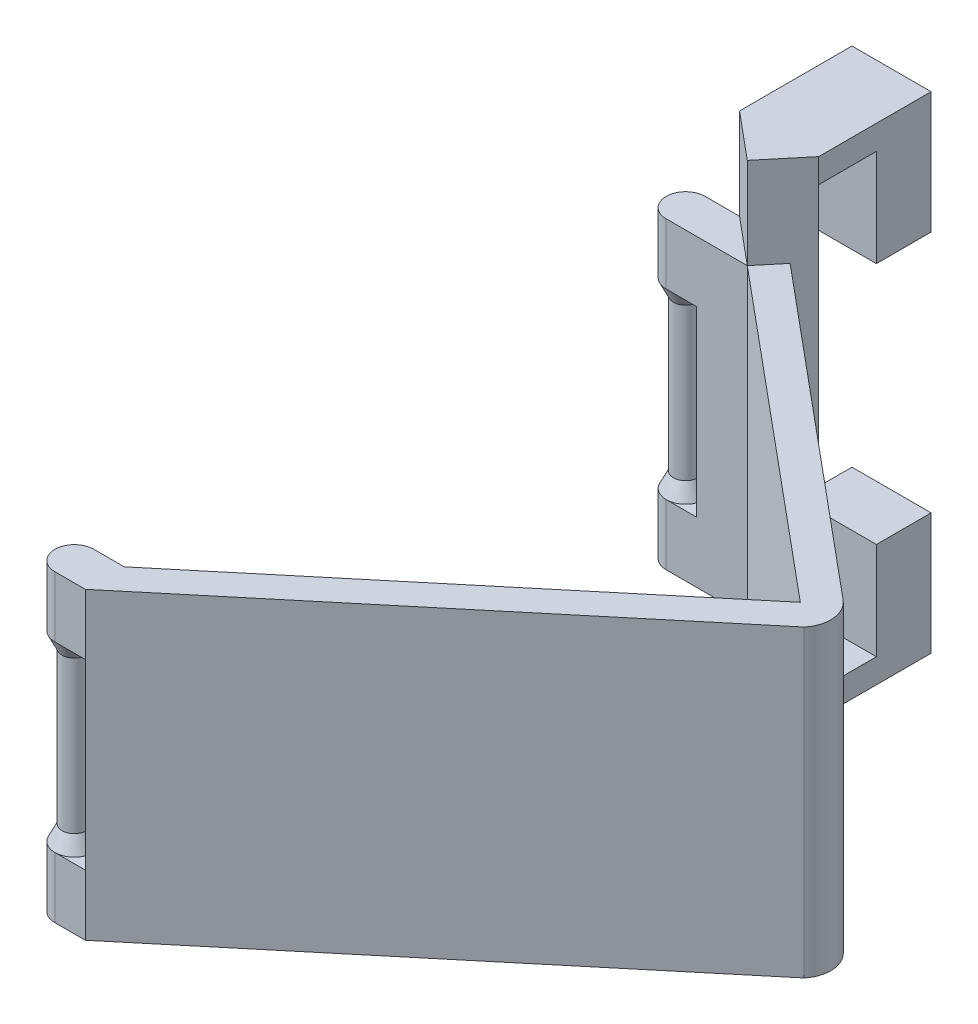
SolidWorks part; units mm, degrees
ref_plane "前视基准面" through (0, 0, 0) normal (0, 0, 1) x (1, 0, 0)
ref_plane "上视基准面" through (0, 0, 0) normal (0, 1, 0) x (1, 0, 0)
ref_plane "右视基准面" through (0, 0, 0) normal (1, 0, 0) x (0, 0, -1)
sketch "草图1" plane through (0, 0, 0) normal (0, 1, 0) x (1, 0, 0)
  line L0 (0, 0) -> (0, 50)
  line L1 (0, 0) -> (-0.664, -50.5533)
  line L2 (0, 0) -> (60, 0)
  line L3 (60, 0) -> (-0.664, -50.5533)
  line L4 (0, 50) -> (60, 0)
  line L5 (60, 0) -> (63.2009, 3.8411)
  line L6 (63.2009, 3.8411) -> (7.8102, 50)
  line L7 (60, 0) -> (63.8411, -3.2009)
  line L8 (63.8411, -3.2009) -> (7.6822, -50)
  line L9 (0, 50) -> (7.8102, 50)
  line L11 (7.6822, -50) -> (-0.664, -56.9551)
  line L12 (-0.664, -56.9551) -> (-0.664, -50.5533)
  arc A0 (63.2009, 3.8411) -> (63.8411, -3.2009) centre (60, 0) cw
extrude "凸台-拉伸1" add sketch "草图1" along normal blind 50 contours L3 L8 L7 | A0 L5 L7 | L9 L4 L5 L6 region at (32.7161, 0, -25.9475) region at (30.6381, 0, 27.7019) region at (62.9887, 0, -0.2717)
sketch "草图3" plane through (27.7911, 0, -33.3493) normal (0.6402, 0, -0.7682) x (-0.7682, 0, -0.6402)
  line L0 (-46.0933, 25) -> (26.0092, 25) construction
  line L1 (-46.0933, 50) -> (-46.0933, 0) construction
  line L2 (26.0092, 50) -> (26.0092, 0) construction
ref_plane "基准面1" through (0, 25, 0) normal (0, -1, 0) x (-0.7682, 0, -0.6402)
sketch "草图4" plane through (0, 50, 0) normal (0, 1, 0) x (1, 0, 0)
  line L0 (0, 50) -> (7.6822, 43.5982)
  line L1 (0, 50) -> (60, 0) construction
  line L2 (7.6822, 43.5982) -> (10.8831, 47.4393)
  line L3 (63.2009, 3.8411) -> (7.8102, 50) construction
  line L4 (10.8831, 47.4393) -> (7.8102, 50)
  line L5 (7.8102, 50) -> (0, 50)
  line L6 (7.8102, 50) -> (19.6167, 50)
  line L7 (10.8831, 47.4393) -> (13.0171, 50)
  line M4 (63.2009, 3.8411) -> (7.8102, 50)
  line M5 (7.8102, 50) -> (0, 50)
  line M6 (0, 50) -> (60, 0)
extrude "凸台-拉伸3" add sketch "草图4" along normal blind 15 and the other way blind 50 contours L2 M6 M4 M5 | L7 L6 M4 region at (6.2006, 50, -47.6222) region at (10.5702, 50, -49.1464)
sketch "草图5" plane through (0, 0, -50) normal (0, 0, -1) x (-1, 0, 0)
  line L0 (-13.0171, 65) -> (-13.0171, 61)
  line L1 (-13.0171, 0) -> (-13.0171, 65) construction
  line L2 (-13.0171, 61) -> (0, 61)
  line L3 (0, 65) -> (0, 0) construction
  line L4 (0, 61) -> (0, 65)
  line L5 (0, 65) -> (-13.0171, 65)
extrude "凸台-拉伸4" add sketch "草图5" along normal blind 18.5
sketch "草图6" plane through (0, 61, 0) normal (0, -1, 0) x (1, 0, 0)
  line L0 (0, -68.5) -> (0, -59.5)
  line L1 (0, -68.5) -> (0, -50) construction
  line L2 (13.0171, -68.5) -> (0, -68.5) construction
  line L3 (0, -59.5) -> (13.0171, -59.5)
  line L4 (13.0171, -68.5) -> (13.0171, -50) construction
  line L5 (13.0171, -59.5) -> (13.0171, -68.5)
  line L6 (13.0171, -68.5) -> (0, -68.5)
extrude "凸台-拉伸5" add sketch "草图6" along normal blind 16
mirror "镜向4" about plane through (0, 25, 0) normal (0, -1, 0) of "凸台-拉伸5", "凸台-拉伸3", "凸台-拉伸4"
sketch "草图7" plane through (0, 50, 0) normal (0, 1, 0) x (1, 0, 0)
  line L0 (-0.664, -53.7542) -> (-5.664, -53.7542)
  line L1 (-0.664, -56.9551) -> (-0.664, -50.5533) construction
  line L2 (-5.664, -53.7542) -> (-5.664, 89.3377)
sketch "草图8" plane through (0, 50, 0) normal (0, 1, 0) x (1, 0, 0)
  line L0 (-0.664, -50.5533) -> (-0.664, 65.3859)
  line L1 (7.6822, 43.5982) -> (-0.664, 43.5982)
  line L2 (-0.664, 43.5982) -> (-0.664, 50)
  line L3 (-0.664, 50) -> (0, 50)
  line L4 (0, 50) -> (7.6822, 43.5982)
extrude "凸台-拉伸6" add sketch "草图8" against normal blind 50 contours L1 L2 L3 L4
sketch "草图9" plane through (0, 0, 0) normal (0, -1, 0) x (1, 0, 0)
  line L0 (-0.664, 56.9551) -> (-5.664, 56.9551)
  line L1 (-0.664, 50.5533) -> (-5.664, 50.5533)
  line L2 (-5.664, 53.7542) -> (-5.664, -89.3377) construction
  line L3 (-0.664, 56.9551) -> (-0.664, 50.5533)
  line L4 (-5.664, 56.9551) -> (-5.664, 50.5533)
  arc A0 (-5.664, 56.9551) -> (-5.664, 50.5533) centre (-5.664, 53.7542) ccw
  line M5 (-0.664, 56.9551) -> (-0.664, 50.5533)
extrude "凸台-拉伸7" add sketch "草图9" against normal blind 10 contours L0 L4 L1 M5 | L4 A0 region at (-3.164, 0, 53.7542) region at (-7.0225, 0, 53.7542)
sketch "草图10" plane through (0, 0, 0) normal (0, -1, 0) x (1, 0, 0)
  line L0 (-0.664, -43.5982) -> (-5.664, -43.5982)
  line L1 (-5.664, 53.7542) -> (-5.664, -89.3377) construction
  line L2 (-0.664, -50) -> (-5.664, -50)
  line L3 (-5.664, -43.5982) -> (-5.664, -50)
  arc A0 (-5.664, -43.5982) -> (-5.664, -50) centre (-5.664, -46.7991) ccw
  line M3 (-0.664, -43.5982) -> (-0.664, -50)
extrude "凸台-拉伸8" add sketch "草图10" against normal blind 10 contours L0 L3 L2 M3 | L3 A0 region at (-3.164, 0, -46.7991) region at (-7.0225, 0, -46.7991)
mirror "镜向5" about plane through (0, 25, 0) normal (0, -1, 0) of "凸台-拉伸8", "凸台-拉伸7"
sketch "草图11" plane through (0, 40, 0) normal (0, -1, 0) x (1, 0, 0)
  circle A0 centre (-5.664, 53.7542) radius 2
extrude "凸台-拉伸9" add sketch "草图11" along normal blind 30
ref_plane "基准面3" through (0, 0, 53.7542) normal (0, 0, -1) x (-1, 0, 0)
sketch "草图14" plane through (0, 0, 53.7542) normal (0, 0, -1) x (-1, 0, 0)
  line L5 (7.664, 10) -> (8.8649, 10)
  line L6 (7.664, 10) -> (7.664, 12.5)
  line L7 (7.664, 10) -> (7.664, 40) construction
  line L8 (7.664, 12.5) -> (8.8649, 10)
ref_axis "基准轴2" through (-5.664, 10, 53.7542) along (0, 1, 0)
revolve "旋转1" add sketch "草图14" angle 360 about axis through (-5.664, 10, 53.7542) along (0, 1, 0) region at (-8.0643, 10.8333, 53.7542)
mirror "镜向6" about plane through (0, 25, 0) normal (0, -1, 0) of "旋转1"
sketch "草图15" plane through (0, 10, 0) normal (0, 1, 0) x (1, 0, 0)
  circle A0 centre (-5.664, 46.7991) radius 2
extrude "凸台-拉伸10" add sketch "草图15" along normal blind 30
sketch "草图16" plane through (0, 0, 0) normal (0, -1, 0) x (1, 0, 0)
  line L0 (-5.664, -46.7991) -> (2.4555, -46.7991)
ref_plane "基准面4" through (0, 0, -46.7991) normal (0, 0, 1) x (1, 0, 0)
ref_axis "基准轴3" through (-5.664, 40, -46.7991) along (0, -1, 0)
sketch "草图17" plane through (0, 0, -46.7991) normal (0, 0, 1) x (1, 0, 0)
  line L0 (-7.664, 10) -> (-7.664, 12.5)
  line L1 (-5.664, 10) -> (-8.8649, 10) construction
  line L2 (-7.664, 12.5) -> (-8.8649, 10)
  line L3 (-8.8649, 10) -> (-7.664, 10)
revolve "旋转2" add sketch "草图17" angle 360 about axis through (-5.664, 40, -46.7991) along (0, -1, 0)
mirror "镜向7" about plane through (0, 25, 0) normal (0, -1, 0) of "旋转2"
